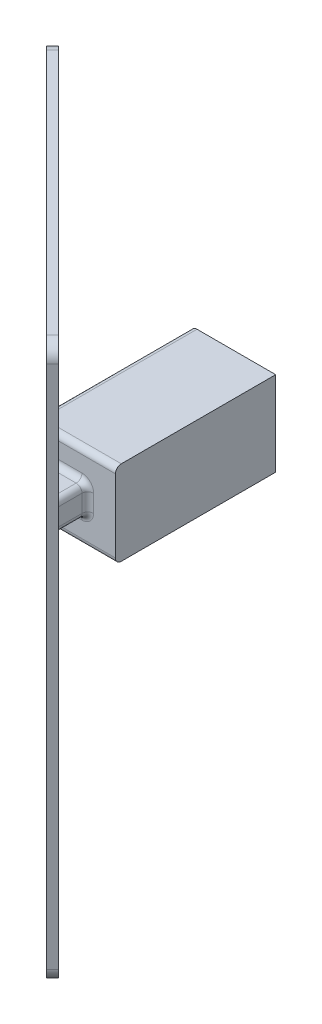
SolidWorks part; units mm, degrees
ref_plane "前视基准面" through (0, 0, 0) normal (0, 0, 1) x (1, 0, 0)
ref_plane "上视基准面" through (0, 0, 0) normal (0, 1, 0) x (1, 0, 0)
ref_plane "右视基准面" through (0, 0, 0) normal (1, 0, 0) x (0, 0, -1)
other "Configuration Table"
sketch "草图1" plane through (0, 0, 0) normal (0, 0, 1) x (1, 0, 0)
  line L0 (14.5, 14.5) -> (-14.5, 14.5)
  line L1 (9.5, -9.5) -> (-9.5, -9.5)
  line L2 (9.5, -9.5) -> (9.5, 9.5)
  line L3 (9.5, 9.5) -> (-9.5, 9.5)
  line L4 (-9.5, -9.5) -> (-9.5, 9.5)
  line L5 (9.5, -9.5) -> (-9.5, 9.5) construction
  line L6 (9.5, 9.5) -> (-9.5, -9.5) construction
  line L7 (-14.5, -14.5) -> (-14.5, 14.5)
  line L8 (14.5, -14.5) -> (-14.5, -14.5)
  line L9 (14.5, -14.5) -> (14.5, 14.5)
  point P0 (0, 0)
  dimension "D1" = 19
  dimension "D2" = 5
extrude "凸台-拉伸1" add sketch "草图1" along normal blind 50
sketch "草图2" plane through (0, 0, 50) normal (0, 0, 1) x (1, 0, 0)
  line L4 (14.5, -14.5) -> (14.5, 14.5)
  line L5 (14.5, 14.5) -> (-14.5, 14.5)
  line L6 (-14.5, 14.5) -> (-14.5, -14.5)
  line L7 (-14.5, -14.5) -> (14.5, -14.5)
  line L8 (14.5, -14.5) -> (14.5, 14.5)
  line L9 (14.5, 14.5) -> (-14.5, 14.5)
  line L10 (-14.5, 14.5) -> (-14.5, -14.5)
  line L11 (-14.5, -14.5) -> (14.5, -14.5)
  dimension "D1" = 0
extrude "凸台-拉伸2" add sketch "草图2" along normal blind 5
sketch "草图3" plane through (0, 0, 55) normal (0, 0, 1) x (1, 0, 0)
  line L1 (5, -5) -> (-5, -5)
  line L2 (5, -5) -> (5, 5)
  line L3 (5, 5) -> (-5, 5)
  line L4 (-5, -5) -> (-5, 5)
  line L5 (5, -5) -> (-5, 5) construction
  line L6 (5, 5) -> (-5, -5) construction
  point P0 (0, 0)
  dimension "D1" = 10
  dimension "D2" = 10
extrude "凸台-拉伸3" add sketch "草图3" along normal blind 10
sketch "草图4" plane through (0, 5, 0) normal (0, 1, 0) x (1, 0, 0)
  line L0 (-5, -55) -> (5, -65)
  line L4 (5, -55) -> (-5, -55)
  line L5 (-5, -55) -> (-5, -65)
  line L6 (-5, -65) -> (5, -65)
  line L7 (5, -65) -> (5, -55)
  line L8 (5, -55) -> (-5, -55)
  line L9 (-5, -55) -> (-5, -65)
  line L10 (-5, -65) -> (5, -65)
  line L11 (5, -65) -> (5, -55)
  line M6 (-5, -55) -> (-5, -65)
  line M7 (-5, -65) -> (5, -65)
  dimension "D1" = 0
extrude "切除-拉伸1" cut sketch "草图4" against normal blind 10 contours L0 M6 M7 region at (-1.6667, 5, 61.6667)
sketch "草图7" plane through (-30, 0, 30) normal (-0.7071, 0, 0.7071) x (0.7071, 0, 0.7071)
  line L0 (35.3553, -5) -> (49.4975, -5) construction
  line L1 (49.4975, 5) -> (45.4975, 5) construction
  line L2 (49.4975, 5) -> (49.4975, -5) construction
  line L3 (49.4975, -5) -> (45.4975, -5) construction
  line L4 (45.4975, 5) -> (45.4975, -5) construction
  line L5 (49.4975, 5) -> (45.4975, -5) construction
  line L6 (49.4975, -5) -> (45.4975, 5) construction
  line L8 (112.4975, -95) -> (-17.5025, -95)
  line L9 (112.4975, -95) -> (112.4975, 95)
  line L10 (112.4975, 95) -> (-17.5025, 95)
  line L11 (-17.5025, -95) -> (-17.5025, 95)
  line L12 (112.4975, -95) -> (-17.5025, 95) construction
  line L13 (112.4975, 95) -> (-17.5025, -95) construction
  point P4 (47.4975, 0)
  point P8 (47.4975, 0)
  dimension "D1" = 4
  dimension "D2" = 130
  dimension "D3" = 190
extrude "凸台-拉伸4" add sketch "草图7" along normal blind 3
sketch "草图8" plane through (0, -14.5, 0) normal (0, -1, 0) x (1, 0, 0)
  line L3 (-14.5, 55) -> (-14.5, 49.7426)
  line L4 (-14.5, 49.7426) -> (-9.2426, 55)
  line L5 (-9.2426, 55) -> (-14.5, 55)
  line L6 (-14.5, 55) -> (-14.5, 49.7426)
  line L7 (-14.5, 49.7426) -> (-9.2426, 55)
  line L8 (-9.2426, 55) -> (-14.5, 55)
  dimension "D1" = 0
extrude "切除-拉伸2" cut sketch "草图8" against normal through all
sketch "草图10" plane through (-32.1213, 0, 32.1213) normal (-0.7071, 0, 0.7071) x (0.7071, 0, 0.7071)
  line L0 (112.4975, 95) -> (-17.5025, 95) construction
  line L2 (-17.5025, 95) -> (-17.5025, -95) construction
  line L3 (112.4975, -95) -> (112.4975, 95) construction
  line L4 (-17.5025, -95) -> (112.4975, -95) construction
  circle A0 centre (107.4975, 90) radius 1.25
  circle A1 centre (-12.5025, 90) radius 1.25
  circle A2 centre (-12.5025, -91) radius 1.25
  circle A3 centre (107.4975, -90) radius 1.25
  dimension "D1" = 2.5
  dimension "D2" = 5
  dimension "D3" = 5
  dimension "D4" = 5
  dimension "D5" = 5
  dimension "D6" = 5
  dimension "D7" = 4
  dimension "D8" = 5
  dimension "D9" = 5
extrude "切除-拉伸3" cut sketch "草图10" against normal through all
sketch "草图11" plane through (-32.1213, 0, 32.1213) normal (-0.7071, 0, 0.7071) x (0.7071, 0, 0.7071)
  line L0 (92.4975, 75) -> (102.4975, 85)
  line L1 (2.4975, 75) -> (-7.5025, 85)
  line L2 (2.4975, -75) -> (-7.5025, -85)
  line L3 (92.4975, -75) -> (102.4975, -85)
  line L4 (94.6188, 72.8787) -> (104.6188, 82.8787)
  line L5 (4.6188, 77.1213) -> (-5.3812, 87.1213)
  line L6 (0.3762, -72.8787) -> (-9.6238, -82.8787)
  line L7 (90.3762, -77.1213) -> (100.3762, -87.1213)
  line L8 (92.4975, 75) -> (2.4975, 75)
  line L9 (2.4975, 75) -> (2.4975, -75)
  line L10 (2.4975, -75) -> (92.4975, -75)
  line L11 (92.4975, -75) -> (92.4975, 75)
  line L12 (92.4975, 75) -> (2.4975, 75)
  line L13 (2.4975, 75) -> (2.4975, -75)
  line L14 (2.4975, -75) -> (92.4975, -75)
  line L15 (92.4975, -75) -> (92.4975, 75)
  line L16 (112.4975, 95) -> (-17.5025, 95)
  line L17 (-17.5025, 95) -> (-17.5025, -95)
  line L18 (-17.5025, -95) -> (112.4975, -95)
  line L19 (112.4975, -95) -> (112.4975, 95)
  line L20 (112.4975, 95) -> (-17.5025, 95) construction
  line L21 (-17.5025, 95) -> (-17.5025, -95) construction
  line L22 (-17.5025, -95) -> (112.4975, -95) construction
  line L23 (112.4975, -95) -> (112.4975, 95) construction
  line L24 (92.4975, 78) -> (2.4975, 78)
  line L25 (-0.5025, 75) -> (-0.5025, -75)
  line L26 (2.4975, -78) -> (92.4975, -78)
  line L27 (95.4975, -75) -> (95.4975, 75)
  line L28 (102.4975, 85) -> (-7.5025, 85)
  line L29 (-7.5025, 85) -> (-7.5025, -85)
  line L30 (-7.5025, -85) -> (102.4975, -85)
  line L31 (102.4975, -85) -> (102.4975, 85)
  line L32 (102.4975, 85) -> (-7.5025, 85)
  line L33 (-7.5025, 85) -> (-7.5025, -85)
  line L34 (-7.5025, -85) -> (102.4975, -85)
  line L35 (102.4975, -85) -> (102.4975, 85)
  line L36 (102.4975, 88) -> (-7.5025, 88)
  line L37 (-10.5025, 85) -> (-10.5025, -85)
  line L38 (-7.5025, -88) -> (102.4975, -88)
  line L39 (105.4975, -85) -> (105.4975, 85)
  line L40 (90.3762, 77.1213) -> (100.3762, 87.1213)
  line L41 (0.3762, 72.8787) -> (-9.6238, 82.8787)
  line L42 (4.6188, -77.1213) -> (-5.3812, -87.1213)
  line L43 (94.6188, -72.8787) -> (104.6188, -82.8787)
  line L44 (92.4975, 72) -> (2.4975, 72)
  line L45 (5.4975, 75) -> (5.4975, -75)
  line L46 (2.4975, -72) -> (92.4975, -72)
  line L47 (89.4975, -75) -> (89.4975, 75)
  line L48 (102.4975, 82) -> (-7.5025, 82)
  line L49 (-4.5025, 85) -> (-4.5025, -85)
  line L50 (-7.5025, -82) -> (102.4975, -82)
  line L51 (99.4975, -85) -> (99.4975, 85)
  dimension "D1" = 20
  dimension "D2" = 0
  dimension "D3" = 10
  dimension "D4" = 3
  dimension "D5" = 3
extrude "切除-拉伸9" cut sketch "草图11" against normal blind 3 contours L42 L50 L7 L26 | L43 L51 L4 L27 | L41 L49 L6 L25 | L40 L48 L5 L24 region at (1.4645, 80.0291, 65.7071) region at (36.8323, 0, 101.0749) region at (-33.9033, 0, 30.3393) region at (1.4645, -80.0291, 65.7071)
fillet "圆角1" radius 2 25 edges at (5, 0, 55) (0, 5, 55) (5, 5, 60) (5, -5, 60) (0, -5, 55) (4.75, -14.5, 55) (-14.5, -14.5, 22.75) (-14.5, 14.5, 22.75) (4.75, 14.5, 55) (-28.416, 78, 33.7053) (-31.2444, 82, 30.8769) (36.2947, 82, 98.416) (33.4663, 78, 95.5876) (-31.416, -73.7574, 30.7053) (-34.2444, -77.7574, 27.8769) (-34.2444, 77.7574, 27.8769) (-31.416, 73.7574, 30.7053) (36.4663, 73.7574, 98.5876) (39.2947, 77.7574, 101.416) (39.2947, -77.7574, 101.416) (36.4663, -73.7574, 98.5876) (33.4663, -78, 95.5876) (-31.2444, -82, 30.8769) (-28.416, -78, 33.7053) (36.2947, -82, 98.416)
fillet "圆角3" radius 5 4 edges at (-43.4368, 95, 18.6845) (-43.4368, -95, 18.6845) (48.4871, -95, 110.6084) (48.4871, 95, 110.6084)
